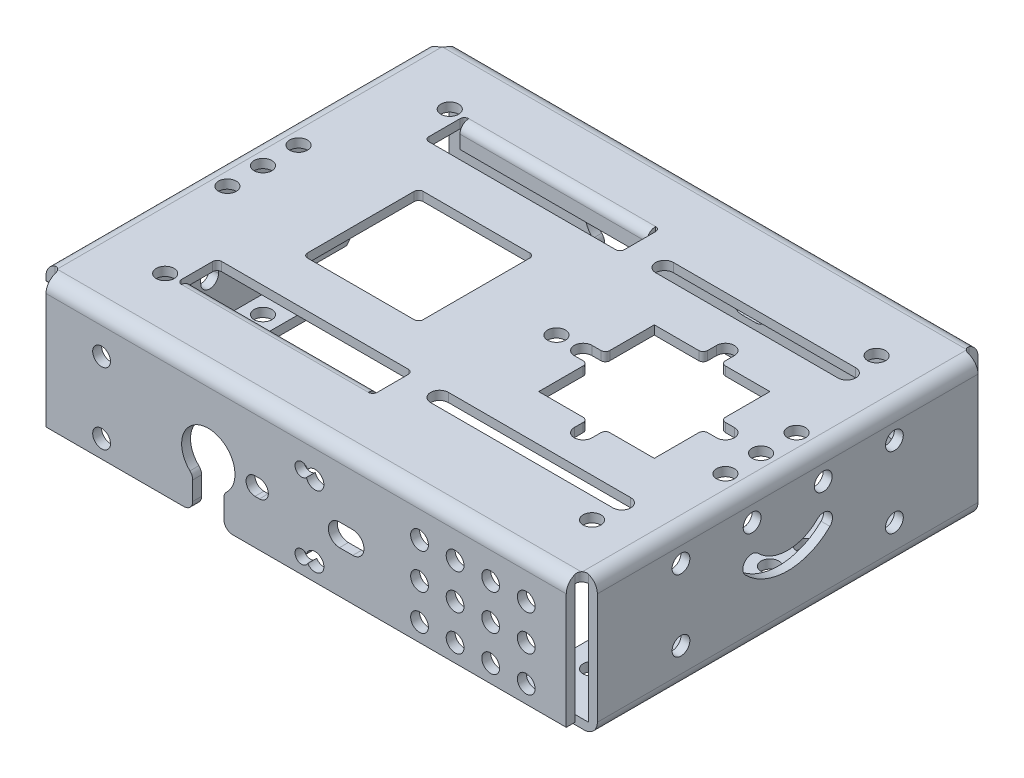
SolidWorks part; units mm, degrees
note: The reader was unsure of these and kept them because the rebuilt part matched: shared geometry of "草图3<2>".
ref_plane "前视基准面" through (0, 0, 0) normal (0, 0, 1) x (1, 0, 0)
ref_plane "上视基准面" through (0, 0, 0) normal (0, 1, 0) x (1, 0, 0)
ref_plane "右视基准面" through (0, 0, 0) normal (1, 0, 0) x (0, 0, -1)
other "Configuration Table"
sketch "草图1" plane through (0, 0, 0) normal (0, 1, 0) x (1, 0, 0)
  line L1 (-62, -46.3) -> (62, -46.3)
  line L2 (-62, -46.3) -> (-62, 46.3)
  line L3 (-62, 46.3) -> (62, 46.3)
  line L4 (62, -46.3) -> (62, 46.3)
  line L5 (-62, -46.3) -> (62, 46.3) construction
  line L6 (-62, 46.3) -> (62, -46.3) construction
  point P0 (0, 0)
  dimension "D1" = 124
  dimension "D2" = 92.6
extrude "凸台-拉伸1" add sketch "草图1" along normal blind 29
shell "抽壳1" thickness 2 removed face at (0, 0, 0)
sketch "草图2" plane through (62, 0, 0) normal (1, 0, 0) x (0, 0, -1)
  line L0 (0, 0) -> (0, 29) construction
  line L1 (-46.3, 0) -> (46.3, 0) construction
  line L2 (-46.3, 29) -> (46.3, 29) construction
  line L3 (-6.6708, 15.8292) -> (-9.4992, 13.0008) construction
  line L4 (6.6708, 15.8292) -> (9.4992, 13.0008) construction
  line L5 (8, 22.5) -> (-8, 22.5) construction
  circle A0 centre (-8, 22.5) radius 2
  circle A1 centre (-24, 22.5) radius 2
  circle A5 centre (-24, 6.5) radius 2
  circle A6 centre (24, 6.5) radius 2
  circle A7 centre (24, 22.5) radius 2
  circle A8 centre (8, 22.5) radius 2
  arc A9 (-6.6708, 15.8292) -> (-9.4992, 13.0008) centre (-8.085, 14.415) ccw
  arc A10 (9.4992, 13.0008) -> (6.6708, 15.8292) centre (8.085, 14.415) ccw
  arc A11 (-9.4992, 13.0008) -> (9.4992, 13.0008) centre (0, 22.5) ccw
  arc A12 (-6.6708, 15.8292) -> (6.6708, 15.8292) centre (0, 22.5) ccw
  point P34 (-8.085, 14.415)
  dimension "D1" = 4
  dimension "D2" = 4
  dimension "D5" = 4
  dimension "D7" = 16
  dimension "D3" = 16
  dimension "D4" = 8
  dimension "D6" = 6.5
  dimension "D8" = 4
  dimension "D9" = 8.085
  dimension "D10" = 90
extrude "切除-拉伸1" cut sketch "草图2" against normal blind 32
sketch "草图3" plane through (62, 0, 0) normal (1, 0, 0) x (0, 0, -1)
  line L0 (-46.3, 29) -> (46.3, 29) construction
  line L1 (-46.3, 29) -> (-42.8, 29)
  line L2 (-46.3, 29) -> (-46.3, 0)
  line L3 (-46.3, 0) -> (-42.8, 0)
  line L4 (-42.8, 29) -> (-42.8, 0)
  line L5 (-46.3, 0) -> (46.3, 0) construction
  line L6 (46.3, 29) -> (46.3, 0) construction
  line L7 (46.3, 29) -> (42.8, 29)
  line L8 (46.3, 29) -> (46.3, 0)
  line L9 (46.3, 0) -> (42.8, 0)
  line L10 (42.8, 29) -> (42.8, 0)
  line L11 (-46.3, 29) -> (-46.3, 0) construction
  dimension "D1" = 3.5
  dimension "D2" = 3.5
extrude "切除-拉伸2" cut sketch "草图3" against normal blind 3.5
extrude "切除-拉伸3" cut sketch "草图3<2>" along normal blind 3.5 from surface at -124 starting at face at (-62, 14.5, 0)
sketch "草图3<2>" plane through (62, 0, 0) normal (1, 0, 0) x (0, 0, -1) same geometry as "草图3"
sketch "草图4" plane through (-62, 0, 0) normal (-1, 0, 0) x (0, 0, 1)
  line L8 (0, 0) -> (0, 29) construction
  line L9 (-42.8, 29) -> (42.8, 29) construction
  line L10 (0, 9.1716) -> (-6, 15.1716)
  line L11 (-6, 15.1716) -> (-6, 9)
  line L12 (-10, 9) -> (-10, 20)
  line L13 (-6.5858, 21.4142) -> (0, 14.8284)
  line L14 (0, 14.8284) -> (6.5858, 21.4142)
  line L15 (10, 20) -> (10, 9)
  line L16 (6, 9) -> (6, 15.1716)
  line L17 (6, 15.1716) -> (0, 9.1716)
  line L18 (-42.8, 0) -> (42.8, 0) construction
  arc A4 (-6, 9) -> (-10, 9) centre (-8, 9) cw
  arc A5 (-10, 20) -> (-6.5858, 21.4142) centre (-8, 20) cw
  arc A6 (6.5858, 21.4142) -> (10, 20) centre (8, 20) cw
  arc A7 (10, 9) -> (6, 9) centre (8, 9) cw
  dimension "D1" = 2
  dimension "D2" = 2
  dimension "D3" = 4
  dimension "D4" = 4
  dimension "D5" = 4
  dimension "D6" = 4
  dimension "D7" = 12
  dimension "D8" = 9
  dimension "D9" = 9
  dimension "D10" = 45
extrude "切除-拉伸4" cut sketch "草图4" against normal blind 3.5
sketch "草图5" plane through (-62, 0, 0) normal (-1, 0, 0) x (0, 0, 1)
  line L0 (-42.8, 25) -> (-22.8, 0)
  line L1 (-42.8, 29) -> (-42.8, 0) construction
  line L2 (-42.8, 0) -> (42.8, 0) construction
  line L3 (-22.8, 0) -> (-13.5, 0)
  line L4 (22.8, 0) -> (42.8, 25)
  line L5 (42.8, 0) -> (42.8, 29) construction
  line L6 (42.8, 25) -> (42.8, -10.1592)
  line L7 (42.8, -10.1592) -> (-42.8, -10.1592)
  line L8 (-42.8, 25) -> (-42.8, -10.1592)
  line L9 (-44.3, 27) -> (-42.8, 27) construction
  line L10 (-13.5, 0) -> (-13.5, 3)
  line L11 (-11.5, 3) -> (-11.5, 0)
  line L12 (11.5, 0) -> (11.5, 3)
  line L13 (13.5, 3) -> (13.5, 0)
  line L14 (-11.5, 0) -> (11.5, 0)
  line L15 (13.5, 0) -> (22.8, 0)
  arc A0 (-13.5, 3) -> (-11.5, 3) centre (-12.5, 3) cw
  arc A1 (11.5, 3) -> (13.5, 3) centre (12.5, 3) cw
  dimension "D8" = 1
  dimension "D9" = 1
  dimension "D1" = 2
  dimension "D2" = 20
  dimension "D3" = 20
  dimension "D4" = 25
  dimension "D5" = 12.5
  dimension "D6" = 3
  dimension "D7" = 3
extrude "切除-拉伸5" cut sketch "草图5" against normal blind 3.5
sketch "草图6" plane through (-62, 0, 0) normal (-1, 0, 0) x (0, 0, 1)
  line L0 (11.5, 3) -> (11.5, 0) construction
  line L1 (-11.5, 0) -> (11.5, 0)
  line L2 (-11.5, 0) -> (-11.5, -2)
  line L3 (-11.5, -2) -> (11.5, -2)
  line L4 (11.5, 0) -> (11.5, -2)
  dimension "D1" = 2
extrude "凸台-拉伸2" add sketch "草图6" against normal blind 10
sketch "草图7" plane through (62, 0, 0) normal (1, 0, 0) x (0, 0, -1)
  line L0 (-42.8, 0) -> (42.8, 0) construction
  line L1 (-42.8, 0) -> (42.8, 0)
  line L2 (-42.8, 0) -> (-42.8, -2)
  line L3 (-42.8, -2) -> (42.8, -2)
  line L4 (42.8, 0) -> (42.8, -2)
  line L5 (42.8, 29) -> (42.8, 0) construction
  line L6 (-42.8, 0) -> (-42.8, 29) construction
  dimension "D1" = 2
extrude "凸台-拉伸3" add sketch "草图7" against normal blind 18
fillet "圆角2" radius 3 6 edges at (62, 29, 0) (0, 29, -46.3) (0, 29, 46.3) (-62, 29, 0) (62, -2, 0) (-62, -2, 0)
fillet "圆角3" radius 1.5 4 edges at (58.5, 28, -42.8) (-58.5, 28, 42.8) (-58.5, 28, -42.8) (58.5, 28, 42.8)
fillet "圆角4" radius 1 3 edges at (-61, 14.8284, 0) (-61, 15.1716, 6) (-61, 15.1716, -6)
sketch "草图8" plane through (0, 0, 0) normal (0, -1, 0) x (1, 0, 0)
  line L1 (44, 42.8) -> (44, -42.8) construction
  line L2 (-56, 0) -> (44, 0) construction
  line L3 (-52, -11.5) -> (-52, 11.5) construction
  circle A0 centre (-56, 0) radius 2
  circle A1 centre (-56, 8) radius 2
  circle A2 centre (-56, -8) radius 2
  circle A3 centre (50, 0) radius 2
  circle A4 centre (50, 8) radius 2
  circle A5 centre (50, -8) radius 2
  circle A6 centre (50, -16) radius 2
  circle A7 centre (50, 16) radius 2
  circle A8 centre (50, 32) radius 2
  circle A9 centre (50, -32) radius 2
  dimension "D1" = 4
  dimension "D2" = 4
  dimension "D5" = 4
  dimension "D8" = 4
  dimension "D3" = 4
  dimension "D4" = 4
  dimension "D6" = 4
  dimension "D7" = 4
  dimension "D9" = 4
  dimension "D10" = 4
  dimension "D11" = 8
  dimension "D12" = 8
  dimension "D13" = 8
  dimension "D14" = 8
  dimension "D15" = 16
  dimension "D16" = 16
  dimension "D17" = 6
  dimension "D18" = 8
  dimension "D19" = 8
  dimension "D20" = 4
extrude "切除-拉伸6" cut sketch "草图8" along normal blind 3
sketch "草图9" plane through (0, 0, -46.3) normal (0, 0, -1) x (-1, 0, 0)
  line L4 (0, 26) -> (0, 0) construction
  line L15 (58.5, 26) -> (-58.5, 26) construction
  line L16 (-25.5, 20) -> (-33.5, 20) construction
  line L17 (46, 12) -> (22, 12) construction
  line L18 (46, 20) -> (46, 4) construction
  line L19 (18.5, 0) -> (18.5, 7.1266)
  line L20 (25.5, 0) -> (18.5, 0)
  line L21 (25.5, 7.1266) -> (25.5, 0)
  line L22 (-7.5, 12) -> (-10.5, 12) construction
  line L23 (-7.5, 14.5) -> (-10.5, 14.5)
  line L24 (-7.5, 9.5) -> (-10.5, 9.5)
  line L25 (11.5, 12) -> (10.5, 12) construction
  line L26 (11.5, 14) -> (10.5, 14)
  line L27 (11.5, 10) -> (10.5, 10)
  circle A25 centre (-25.5, 4) radius 2
  circle A26 centre (-25.5, 12) radius 2
  circle A27 centre (-49.5, 4) radius 2
  circle A28 centre (-41.5, 4) radius 2
  circle A29 centre (-33.5, 4) radius 2
  circle A30 centre (-49.5, 12) radius 2
  circle A31 centre (-41.5, 12) radius 2
  circle A32 centre (-33.5, 12) radius 2
  circle A33 centre (-49.5, 20) radius 2
  circle A34 centre (-41.5, 20) radius 2
  circle A35 centre (-33.5, 20) radius 2
  circle A36 centre (-25.5, 20) radius 2
  arc A37 (-0.0758, 19.4547) -> (-0.3567, 21.1399) centre (1, 20.5) ccw
  arc A38 (-0.3567, 21.1399) -> (-0.0758, 19.4547) centre (-2, 20) ccw
  arc A39 (-0.3567, 2.8601) -> (-0.0758, 4.5453) centre (-2, 4) cw
  arc A40 (-0.0758, 4.5453) -> (-0.3567, 2.8601) centre (1, 3.5) cw
  arc A41 (18.5, 7.1266) -> (25.5, 7.1266) centre (22, 12) cw
  circle A42 centre (46, 20) radius 2
  circle A43 centre (46, 4) radius 2
  arc A44 (-7.5, 14.5) -> (-7.5, 9.5) centre (-7.5, 12) cw
  arc A45 (-10.5, 9.5) -> (-10.5, 14.5) centre (-10.5, 12) cw
  arc A46 (11.5, 14) -> (11.5, 10) centre (11.5, 12) cw
  arc A47 (10.5, 10) -> (10.5, 14) centre (10.5, 12) cw
  point P127 (-9, 12)
  point P134 (11, 12)
extrude "切除-拉伸7" cut sketch "草图9" against normal through all
fillet "圆角5" radius 2 8 edges at (-18.5, 0, -45.3) (-25.5, 0, -45.3) (-18.5, 0, 45.3) (-25.5, 0, 45.3) (-25.5, 7.1266, 45.3) (-18.5, 7.1266, 45.3) (-18.5, 7.1266, -45.3) (-25.5, 7.1266, -45.3)
sketch "草图26" plane through (0, 29, 0) normal (0, 1, 0) x (1, 0, 0)
  line L0 (0, -43.3) -> (0, 43.3) construction
  line L1 (62, 42.8) -> (62, -42.8) construction
  line L2 (9, 25.3) -> (50, 25.3) construction
  line L3 (-42, 32.3) -> (0, 32.3)
  line L4 (-43, 31.3) -> (-43, 24.3)
  line L5 (-42, 23.3) -> (0, 23.3)
  line L6 (1, 31.3) -> (1, 24.3)
  line L7 (9, 27.3) -> (50, 27.3)
  line L8 (9, 23.3) -> (50, 23.3)
  line L9 (-58.882, -43.3) -> (58.882, -43.3) construction
  line L10 (-33, 13) -> (-9, 13)
  line L11 (-34, 12) -> (-34, -12)
  line L12 (-33, -13) -> (-9, -13)
  line L13 (-8, 12) -> (-8, -12)
  line L14 (19, 13) -> (29, 13)
  line L15 (19, 13) -> (19, 3)
  line L16 (19, -13) -> (29, -13)
  line L17 (45, 13) -> (45, 3)
  line L18 (58.882, 43.3) -> (-58.882, 43.3) construction
  line L19 (0.627, 0) -> (59, 0) construction
  line L20 (59, -43.182) -> (59, 43.182) construction
  line L21 (-62, -42.8) -> (-62, 42.8) construction
  line L22 (16, 0) -> (19, 0) construction
  line L23 (16, 2) -> (18, 2)
  line L24 (16, -2) -> (18, -2)
  line L25 (19, -3) -> (19, -13)
  line L26 (19, 13) -> (45, -13) construction
  line L27 (30, 16) -> (30, 14)
  line L28 (34, 16) -> (34, 14)
  line L29 (48, 2) -> (46, 2)
  line L30 (48, -2) -> (46, -2)
  line L31 (34, -16) -> (34, -14)
  line L32 (30, -16) -> (30, -14)
  line L33 (35, 13) -> (45, 13)
  line L34 (45, -3) -> (45, -13)
  line L35 (35, -13) -> (45, -13)
  line L36 (-58.5, 46.3) -> (58.5, 46.3) construction
  line L37 (1, -31.3) -> (1, -24.3)
  line L38 (-42, -23.3) -> (0, -23.3)
  line L39 (-43, -31.3) -> (-43, -24.3)
  line L40 (-42, -32.3) -> (0, -32.3)
  line L41 (9, -25.3) -> (50, -25.3) construction
  line L42 (9, -27.3) -> (50, -27.3)
  line L43 (9, -23.3) -> (50, -23.3)
  line L44 (-46, -32) -> (-46, 32) construction
  circle A0 centre (56, 0) radius 2
  circle A1 centre (56, 8) radius 2
  circle A2 centre (56, -8) radius 2
  circle A3 centre (-56, -8) radius 2
  circle A4 centre (-56, 8) radius 2
  circle A5 centre (-56, 0) radius 2
  arc A6 (9, 27.3) -> (9, 23.3) centre (9, 25.3) ccw
  arc A7 (50, 23.3) -> (50, 27.3) centre (50, 25.3) ccw
  circle A8 centre (10, 0) radius 2
  arc A9 (16, 2) -> (16, -2) centre (16, 0) ccw
  arc A10 (34, 16) -> (30, 16) centre (32, 16) ccw
  arc A11 (48, -2) -> (48, 2) centre (48, 0) ccw
  arc A12 (30, -16) -> (34, -16) centre (32, -16) ccw
  arc A13 (29, 13) -> (30, 14) centre (29, 14) ccw
  arc A14 (35, 13) -> (34, 14) centre (35, 14) cw
  arc A15 (45, 3) -> (46, 2) centre (46, 3) ccw
  arc A16 (46, -2) -> (45, -3) centre (46, -3) ccw
  arc A17 (35, -13) -> (34, -14) centre (35, -14) ccw
  arc A18 (30, -14) -> (29, -13) centre (29, -14) ccw
  arc A19 (19, -3) -> (18, -2) centre (18, -3) ccw
  arc A20 (18, 2) -> (19, 3) centre (18, 3) ccw
  arc A21 (9, -27.3) -> (9, -23.3) centre (9, -25.3) cw
  arc A22 (50, -23.3) -> (50, -27.3) centre (50, -25.3) cw
  circle A23 centre (-46, 32) radius 2
  circle A24 centre (50, 32) radius 2
  circle A25 centre (50, -32) radius 2
  circle A26 centre (-46, -32) radius 2
  arc A27 (-33, -13) -> (-34, -12) centre (-33, -12) cw
  arc A28 (-33, 13) -> (-34, 12) centre (-33, 12) ccw
  arc A29 (-8, 12) -> (-9, 13) centre (-9, 12) ccw
  arc A30 (-8, -12) -> (-9, -13) centre (-9, -12) cw
  arc A31 (1, -24.3) -> (0, -23.3) centre (0, -24.3) ccw
  arc A32 (0, -32.3) -> (1, -31.3) centre (0, -31.3) ccw
  arc A33 (-43, -31.3) -> (-42, -32.3) centre (-42, -31.3) ccw
  arc A34 (-42, -23.3) -> (-43, -24.3) centre (-42, -24.3) ccw
  arc A35 (1, 31.3) -> (0, 32.3) centre (0, 31.3) ccw
  arc A36 (1, 24.3) -> (0, 23.3) centre (0, 24.3) cw
  arc A37 (-43, 24.3) -> (-42, 23.3) centre (-42, 24.3) ccw
  arc A38 (-42, 32.3) -> (-43, 31.3) centre (-42, 31.3) ccw
  point P23 (29.5, 25.3)
  point P38 (17.5, 0)
  point P39 (-8, 0)
  point P42 (32, 0)
  point P75 (32, 0)
  point P98 (29.5, -25.3)
  point P111 (-46, 0)
  point P118 (-34, -13)
  point P121 (-34, 13)
  point P124 (-8, 13)
  point P129 (1, -23.3)
  point P132 (1, -32.3)
  point P135 (-43, -32.3)
  point P138 (-43, -23.3)
  point P141 (1, 32.3)
  point P144 (1, 23.3)
  point P147 (-43, 23.3)
  point P150 (-43, 32.3)
  dimension "D1" = 4
  dimension "D2" = 4
  dimension "D3" = 4
  dimension "D13" = 4
  dimension "D15" = 2
  dimension "D19" = 1
  dimension "D20" = 2
  dimension "D26" = 4
  dimension "D27" = 4
  dimension "D28" = 4
  dimension "D29" = 4
  dimension "D33" = 1
  dimension "D4" = 16
  dimension "D5" = 8
  dimension "D6" = 6
  dimension "D7" = 26
  dimension "D8" = 26
  dimension "D9" = 17
  dimension "D10" = 26
  dimension "D11" = 26
  dimension "D12" = 28
  dimension "D16" = 3
  dimension "D17" = 13
  dimension "D21" = 9
  dimension "D22" = 21
  dimension "D23" = 44
  dimension "D24" = 41
  dimension "D25" = 8
  dimension "D30" = 96
  dimension "D31" = 64
  dimension "D14" = 56
  dimension "D32" = 6
  dimension "D18" = 4
extrude "切除-拉伸8" cut sketch "草图26" against normal blind 3
sketch "草图27" plane through (0, 29, 0) normal (0, 1, 0) x (1, 0, 0)
  line L0 (0, 0) -> (-56, 0) construction
  line L1 (-42, 32.3) -> (0, 32.3)
  line L2 (-42, 32.3) -> (-42, 30.3)
  line L3 (-42, 30.3) -> (0, 30.3)
  line L4 (0, 32.3) -> (0, 30.3)
  line L5 (0, -32.3) -> (0, -30.3)
  line L6 (-42, -30.3) -> (0, -30.3)
  line L7 (-42, -32.3) -> (-42, -30.3)
  line L8 (-42, -32.3) -> (0, -32.3)
  dimension "D1" = 2
extrude "凸台-拉伸4" add sketch "草图27" against normal blind 5
fillet "圆角6" radius 2 2 edges at (-21, 29, 30.3) (-21, 29, -30.3)
thread "螺纹线7" [suppressed] pitch 0.25 start angle 0, offset 0, length 2, pitch 0.25, diameter 4
ref_plane "基准面7" [suppressed] through (-50.5, 32, -32) normal (0, 0, 1) x (-1, 0, 0)
sketch "螺纹线轮廓7" [suppressed] plane through (-50.5, 32, -32) normal (0, 0, 1) x (-1, 0, 0)
  line L0 (0, 0) -> (0, 0.25) construction
  line L1 (0, 0) -> (0.1353, 0.0781)
  line L2 (0.1353, 0.0781) -> (0.1353, 0.1094)
  line L3 (0.1353, 0.1094) -> (0, 0.1875)
  line L4 (0.1353, 0.0937) -> (0, 0.0937) construction
  line L11 (0, 0) -> (0, 0.1875)
  point P2 (0, 0)
  dimension "Pitch" = 0.25
  dimension "Profile_Angle" = 60
  dimension "Profile_Land" = 0.0312
  dimension "Profile_Height" = 0.1353
thread "螺纹线20" [suppressed] pitch 0.25 start angle 0, offset 0, length 2, pitch 0.25, diameter 4
ref_plane "基准面20" [suppressed] through (52, 0, 16) normal (0, 0, 1) x (1, 0, 0)
sketch "螺纹线轮廓20" [suppressed] plane through (52, 0, 16) normal (0, 0, 1) x (1, 0, 0)
  line L0 (0, 0) -> (0, 0.25) construction
  line L1 (0, 0) -> (0.1353, 0.0781)
  line L2 (0.1353, 0.0781) -> (0.1353, 0.1094)
  line L3 (0.1353, 0.1094) -> (0, 0.1875)
  line L4 (0.1353, 0.0937) -> (0, 0.0937) construction
  line L11 (0, 0) -> (0, 0.1875)
  point P2 (0, 0)
  dimension "Pitch" = 0.25
  dimension "Profile_Angle" = 60
  dimension "Profile_Land" = 0.0312
  dimension "Profile_Height" = 0.1353
thread "螺纹线19" [suppressed] pitch 0.25 start angle 0, offset 0, length 2, pitch 0.25, diameter 4
ref_plane "基准面19" [suppressed] through (52, 0, 8) normal (0, 0, 1) x (1, 0, 0)
sketch "螺纹线轮廓19" [suppressed] plane through (52, 0, 8) normal (0, 0, 1) x (1, 0, 0)
  line L0 (0, 0) -> (0, 0.25) construction
  line L1 (0, 0) -> (0.1353, 0.0781)
  line L2 (0.1353, 0.0781) -> (0.1353, 0.1094)
  line L3 (0.1353, 0.1094) -> (0, 0.1875)
  line L4 (0.1353, 0.0937) -> (0, 0.0937) construction
  line L11 (0, 0) -> (0, 0.1875)
  point P2 (0, 0)
  dimension "Pitch" = 0.25
  dimension "Profile_Angle" = 60
  dimension "Profile_Land" = 0.0312
  dimension "Profile_Height" = 0.1353
thread "螺纹线18" [suppressed] pitch 0.25 start angle 0, offset 0, length 2, pitch 0.25, diameter 4
ref_plane "基准面18" [suppressed] through (52, 0, -8) normal (0, 0, 1) x (1, 0, 0)
sketch "螺纹线轮廓18" [suppressed] plane through (52, 0, -8) normal (0, 0, 1) x (1, 0, 0)
  line L0 (0, 0) -> (0, 0.25) construction
  line L1 (0, 0) -> (0.1353, 0.0781)
  line L2 (0.1353, 0.0781) -> (0.1353, 0.1094)
  line L3 (0.1353, 0.1094) -> (0, 0.1875)
  line L4 (0.1353, 0.0937) -> (0, 0.0937) construction
  line L11 (0, 0) -> (0, 0.1875)
  point P2 (0, 0)
  dimension "Pitch" = 0.25
  dimension "Profile_Angle" = 60
  dimension "Profile_Land" = 0.0312
  dimension "Profile_Height" = 0.1353
thread "螺纹线17" [suppressed] pitch 0.25 start angle 0, offset 0, length 2, pitch 0.25, diameter 4
ref_plane "基准面17" [suppressed] through (52, 0, -16) normal (0, 0, 1) x (1, 0, 0)
sketch "螺纹线轮廓17" [suppressed] plane through (52, 0, -16) normal (0, 0, 1) x (1, 0, 0)
  line L0 (0, 0) -> (0, 0.25) construction
  line L1 (0, 0) -> (0.1353, 0.0781)
  line L2 (0.1353, 0.0781) -> (0.1353, 0.1094)
  line L3 (0.1353, 0.1094) -> (0, 0.1875)
  line L4 (0.1353, 0.0937) -> (0, 0.0937) construction
  line L11 (0, 0) -> (0, 0.1875)
  point P2 (0, 0)
  dimension "Pitch" = 0.25
  dimension "Profile_Angle" = 60
  dimension "Profile_Land" = 0.0312
  dimension "Profile_Height" = 0.1353
thread "螺纹线16" [suppressed] pitch 0.25 start angle 0, offset 0, length 2, pitch 0.25, diameter 4
ref_plane "基准面16" [suppressed] through (-54, 0, 8) normal (0, 0, 1) x (1, 0, 0)
sketch "螺纹线轮廓16" [suppressed] plane through (-54, 0, 8) normal (0, 0, 1) x (1, 0, 0)
  line L0 (0, 0) -> (0, 0.25) construction
  line L1 (0, 0) -> (0.1353, 0.0781)
  line L2 (0.1353, 0.0781) -> (0.1353, 0.1094)
  line L3 (0.1353, 0.1094) -> (0, 0.1875)
  line L4 (0.1353, 0.0937) -> (0, 0.0937) construction
  line L11 (0, 0) -> (0, 0.1875)
  point P2 (0, 0)
  dimension "Pitch" = 0.25
  dimension "Profile_Angle" = 60
  dimension "Profile_Land" = 0.0312
  dimension "Profile_Height" = 0.1353
thread "螺纹线15" [suppressed] pitch 0.25 start angle 0, offset 0, length 2, pitch 0.25, diameter 4
ref_plane "基准面15" [suppressed] through (-54, 0, -8) normal (0, 0, 1) x (1, 0, 0)
sketch "螺纹线轮廓15" [suppressed] plane through (-54, 0, -8) normal (0, 0, 1) x (1, 0, 0)
  line L0 (0, 0) -> (0, 0.25) construction
  line L1 (0, 0) -> (0.1353, 0.0781)
  line L2 (0.1353, 0.0781) -> (0.1353, 0.1094)
  line L3 (0.1353, 0.1094) -> (0, 0.1875)
  line L4 (0.1353, 0.0937) -> (0, 0.0937) construction
  line L11 (0, 0) -> (0, 0.1875)
  point P2 (0, 0)
  dimension "Pitch" = 0.25
  dimension "Profile_Angle" = 60
  dimension "Profile_Land" = 0.0312
  dimension "Profile_Height" = 0.1353
thread "螺纹线13" [suppressed] pitch 0.25 start angle 0, offset 0, length 2, pitch 0.25, diameter 4
ref_plane "基准面13" [suppressed] through (54, 32, -8) normal (0, 0, 1) x (-1, 0, 0)
sketch "螺纹线轮廓13" [suppressed] plane through (54, 32, -8) normal (0, 0, 1) x (-1, 0, 0)
  line L0 (0, 0) -> (0, 0.25) construction
  line L1 (0, 0) -> (0.1353, 0.0781)
  line L2 (0.1353, 0.0781) -> (0.1353, 0.1094)
  line L3 (0.1353, 0.1094) -> (0, 0.1875)
  line L4 (0.1353, 0.0937) -> (0, 0.0937) construction
  line L11 (0, 0) -> (0, 0.1875)
  point P2 (0, 0)
  dimension "Pitch" = 0.25
  dimension "Profile_Angle" = 60
  dimension "Profile_Land" = 0.0312
  dimension "Profile_Height" = 0.1353
thread "螺纹线12" [suppressed] pitch 0.25 start angle 0, offset 0, length 2, pitch 0.25, diameter 4
ref_plane "基准面12" [suppressed] through (-58, 32, 8) normal (0, 0, 1) x (-1, 0, 0)
sketch "螺纹线轮廓12" [suppressed] plane through (-58, 32, 8) normal (0, 0, 1) x (-1, 0, 0)
  line L0 (0, 0) -> (0, 0.25) construction
  line L1 (0, 0) -> (0.1353, 0.0781)
  line L2 (0.1353, 0.0781) -> (0.1353, 0.1094)
  line L3 (0.1353, 0.1094) -> (0, 0.1875)
  line L4 (0.1353, 0.0937) -> (0, 0.0937) construction
  line L11 (0, 0) -> (0, 0.1875)
  point P2 (0, 0)
  dimension "Pitch" = 0.25
  dimension "Profile_Angle" = 60
  dimension "Profile_Land" = 0.0312
  dimension "Profile_Height" = 0.1353
thread "螺纹线11" [suppressed] pitch 0.25 start angle 0, offset 0, length 2, pitch 0.25, diameter 4
ref_plane "基准面11" [suppressed] through (-58, 32, -8) normal (0, 0, 1) x (-1, 0, 0)
sketch "螺纹线轮廓11" [suppressed] plane through (-58, 32, -8) normal (0, 0, 1) x (-1, 0, 0)
  line L0 (0, 0) -> (0, 0.25) construction
  line L1 (0, 0) -> (0.1353, 0.0781)
  line L2 (0.1353, 0.0781) -> (0.1353, 0.1094)
  line L3 (0.1353, 0.1094) -> (0, 0.1875)
  line L4 (0.1353, 0.0937) -> (0, 0.0937) construction
  line L11 (0, 0) -> (0, 0.1875)
  point P2 (0, 0)
  dimension "Pitch" = 0.25
  dimension "Profile_Angle" = 60
  dimension "Profile_Land" = 0.0312
  dimension "Profile_Height" = 0.1353
thread "螺纹线10" [suppressed] pitch 0.25 start angle 0, offset 0, length 2, pitch 0.25, diameter 4
ref_plane "基准面10" [suppressed] through (45.5, 32, 32) normal (0, 0, 1) x (-1, 0, 0)
sketch "螺纹线轮廓10" [suppressed] plane through (45.5, 32, 32) normal (0, 0, 1) x (-1, 0, 0)
  line L0 (0, 0) -> (0, 0.25) construction
  line L1 (0, 0) -> (0.1353, 0.0781)
  line L2 (0.1353, 0.0781) -> (0.1353, 0.1094)
  line L3 (0.1353, 0.1094) -> (0, 0.1875)
  line L4 (0.1353, 0.0937) -> (0, 0.0937) construction
  line L11 (0, 0) -> (0, 0.1875)
  point P2 (0, 0)
  dimension "Pitch" = 0.25
  dimension "Profile_Angle" = 60
  dimension "Profile_Land" = 0.0312
  dimension "Profile_Height" = 0.1353
thread "螺纹线9" [suppressed] pitch 0.25 start angle 0, offset 0, length 2, pitch 0.25, diameter 4
ref_plane "基准面9" [suppressed] through (-50.5, 32, 32) normal (0, 0, 1) x (-1, 0, 0)
sketch "螺纹线轮廓9" [suppressed] plane through (-50.5, 32, 32) normal (0, 0, 1) x (-1, 0, 0)
  line L0 (0, 0) -> (0, 0.25) construction
  line L1 (0, 0) -> (0.1353, 0.0781)
  line L2 (0.1353, 0.0781) -> (0.1353, 0.1094)
  line L3 (0.1353, 0.1094) -> (0, 0.1875)
  line L4 (0.1353, 0.0937) -> (0, 0.0937) construction
  line L11 (0, 0) -> (0, 0.1875)
  point P2 (0, 0)
  dimension "Pitch" = 0.25
  dimension "Profile_Angle" = 60
  dimension "Profile_Land" = 0.0312
  dimension "Profile_Height" = 0.1353
thread "螺纹线8" [suppressed] pitch 0.25 start angle 0, offset 0, length 2, pitch 0.25, diameter 4
ref_plane "基准面8" [suppressed] through (45.5, 32, -32) normal (0, 0, 1) x (-1, 0, 0)
sketch "螺纹线轮廓8" [suppressed] plane through (45.5, 32, -32) normal (0, 0, 1) x (-1, 0, 0)
  line L0 (0, 0) -> (0, 0.25) construction
  line L1 (0, 0) -> (0.1353, 0.0781)
  line L2 (0.1353, 0.0781) -> (0.1353, 0.1094)
  line L3 (0.1353, 0.1094) -> (0, 0.1875)
  line L4 (0.1353, 0.0937) -> (0, 0.0937) construction
  line L11 (0, 0) -> (0, 0.1875)
  point P2 (0, 0)
  dimension "Pitch" = 0.25
  dimension "Profile_Angle" = 60
  dimension "Profile_Land" = 0.0312
  dimension "Profile_Height" = 0.1353
thread "螺纹线14" [suppressed] pitch 0.25 start angle 0, offset 0, length 2, pitch 0.25, diameter 4
ref_plane "基准面14" [suppressed] through (54, 32, 8) normal (0, 0, 1) x (-1, 0, 0)
sketch "螺纹线轮廓14" [suppressed] plane through (54, 32, 8) normal (0, 0, 1) x (-1, 0, 0)
  line L0 (0, 0) -> (0, 0.25) construction
  line L1 (0, 0) -> (0.1353, 0.0781)
  line L2 (0.1353, 0.0781) -> (0.1353, 0.1094)
  line L3 (0.1353, 0.1094) -> (0, 0.1875)
  line L4 (0.1353, 0.0937) -> (0, 0.0937) construction
  line L11 (0, 0) -> (0, 0.1875)
  point P2 (0, 0)
  dimension "Pitch" = 0.25
  dimension "Profile_Angle" = 60
  dimension "Profile_Land" = 0.0312
  dimension "Profile_Height" = 0.1353
thread "螺纹线1" [suppressed] pitch 0.25 start angle 0, offset 0, length 2, pitch 0.25, diameter 4
ref_plane "基准面1" [suppressed] through (62, 25.5, 26) normal (0, -1, 0) x (0, 0, 1)
sketch "螺纹线轮廓1" [suppressed] plane through (62, 25.5, 26) normal (0, -1, 0) x (0, 0, 1)
  line L0 (0, 0) -> (0, 0.25) construction
  line L1 (0, 0) -> (0.1353, 0.0781)
  line L2 (0.1353, 0.0781) -> (0.1353, 0.1094)
  line L3 (0.1353, 0.1094) -> (0, 0.1875)
  line L4 (0.1353, 0.0937) -> (0, 0.0937) construction
  line L11 (0, 0) -> (0, 0.1875)
  point P2 (0, 0)
  dimension "Pitch" = 0.25
  dimension "Profile_Angle" = 60
  dimension "Profile_Land" = 0.0312
  dimension "Profile_Height" = 0.1353
thread "螺纹线3" [suppressed] pitch 0.25 start angle 0, offset 0, length 2, pitch 0.25, diameter 4
ref_plane "基准面3" [suppressed] through (62, 25.5, -6) normal (0, -1, 0) x (0, 0, 1)
sketch "螺纹线轮廓3" [suppressed] plane through (62, 25.5, -6) normal (0, -1, 0) x (0, 0, 1)
  line L0 (0, 0) -> (0, 0.25) construction
  line L1 (0, 0) -> (0.1353, 0.0781)
  line L2 (0.1353, 0.0781) -> (0.1353, 0.1094)
  line L3 (0.1353, 0.1094) -> (0, 0.1875)
  line L4 (0.1353, 0.0937) -> (0, 0.0937) construction
  line L11 (0, 0) -> (0, 0.1875)
  point P2 (0, 0)
  dimension "Pitch" = 0.25
  dimension "Profile_Angle" = 60
  dimension "Profile_Land" = 0.0312
  dimension "Profile_Height" = 0.1353
thread "螺纹线4" [suppressed] pitch 0.25 start angle 0, offset 0, length 2, pitch 0.25, diameter 4
ref_plane "基准面4" [suppressed] through (62, 25.5, -22) normal (0, -1, 0) x (0, 0, 1)
sketch "螺纹线轮廓4" [suppressed] plane through (62, 25.5, -22) normal (0, -1, 0) x (0, 0, 1)
  line L0 (0, 0) -> (0, 0.25) construction
  line L1 (0, 0) -> (0.1353, 0.0781)
  line L2 (0.1353, 0.0781) -> (0.1353, 0.1094)
  line L3 (0.1353, 0.1094) -> (0, 0.1875)
  line L4 (0.1353, 0.0937) -> (0, 0.0937) construction
  line L11 (0, 0) -> (0, 0.1875)
  point P2 (0, 0)
  dimension "Pitch" = 0.25
  dimension "Profile_Angle" = 60
  dimension "Profile_Land" = 0.0312
  dimension "Profile_Height" = 0.1353
thread "螺纹线5" [suppressed] pitch 0.25 start angle 0, offset 0, length 2, pitch 0.25, diameter 4
ref_plane "基准面5" [suppressed] through (62, 9.5, 26) normal (0, -1, 0) x (0, 0, 1)
sketch "螺纹线轮廓5" [suppressed] plane through (62, 9.5, 26) normal (0, -1, 0) x (0, 0, 1)
  line L0 (0, 0) -> (0, 0.25) construction
  line L1 (0, 0) -> (0.1353, 0.0781)
  line L2 (0.1353, 0.0781) -> (0.1353, 0.1094)
  line L3 (0.1353, 0.1094) -> (0, 0.1875)
  line L4 (0.1353, 0.0937) -> (0, 0.0937) construction
  line L11 (0, 0) -> (0, 0.1875)
  point P2 (0, 0)
  dimension "Pitch" = 0.25
  dimension "Profile_Angle" = 60
  dimension "Profile_Land" = 0.0312
  dimension "Profile_Height" = 0.1353
thread "螺纹线6" [suppressed] pitch 0.25 start angle 0, offset 0, length 2, pitch 0.25, diameter 4
ref_plane "基准面6" [suppressed] through (62, 9.5, -22) normal (0, -1, 0) x (0, 0, 1)
sketch "螺纹线轮廓6" [suppressed] plane through (62, 9.5, -22) normal (0, -1, 0) x (0, 0, 1)
  line L0 (0, 0) -> (0, 0.25) construction
  line L1 (0, 0) -> (0.1353, 0.0781)
  line L2 (0.1353, 0.0781) -> (0.1353, 0.1094)
  line L3 (0.1353, 0.1094) -> (0, 0.1875)
  line L4 (0.1353, 0.0937) -> (0, 0.0937) construction
  line L11 (0, 0) -> (0, 0.1875)
  point P2 (0, 0)
  dimension "Pitch" = 0.25
  dimension "Profile_Angle" = 60
  dimension "Profile_Land" = 0.0312
  dimension "Profile_Height" = 0.1353
thread "螺纹线2" [suppressed] pitch 0.25 start angle 0, offset 0, length 2, pitch 0.25, diameter 4
ref_plane "基准面2" [suppressed] through (62, 25.5, 10) normal (0, -1, 0) x (0, 0, 1)
sketch "螺纹线轮廓2" [suppressed] plane through (62, 25.5, 10) normal (0, -1, 0) x (0, 0, 1)
  line L0 (0, 0) -> (0, 0.25) construction
  line L1 (0, 0) -> (0.1353, 0.0781)
  line L2 (0.1353, 0.0781) -> (0.1353, 0.1094)
  line L3 (0.1353, 0.1094) -> (0, 0.1875)
  line L4 (0.1353, 0.0937) -> (0, 0.0937) construction
  line L11 (0, 0) -> (0, 0.1875)
  point P2 (0, 0)
  dimension "Pitch" = 0.25
  dimension "Profile_Angle" = 60
  dimension "Profile_Land" = 0.0312
  dimension "Profile_Height" = 0.1353
equation "\"D2@草图2\"=\"D1@草图2\""
equation "\"D5@草图2\"=\"D1@草图2\""
equation "\"D3@草图2\"=\"D7@草图2\""
equation "\"D4@草图2\"=\"D7@草图2\"/2"
equation "\"D8@草图2\"=\"D1@草图2\""
equation "\"D4@草图4\"=\"D3@草图4\""
equation "\"D5@草图4\"=\"D3@草图4\""
equation "\"D6@草图4\"=\"D3@草图4\""
equation "\"D5@草图5\"=\"D4@草图5\"/2"
equation "\"D7@草图5\"=\"D6@草图5\""
equation "\"D2@草图8\"=\"D1@草图8\""
equation "\"D3@草图8\"=\"D1@草图8\""
equation "\"D4@草图8\"=\"D1@草图8\""
equation "\"D5@草图8\"=\"D1@草图8\""
equation "\"D6@草图8\"=\"D1@草图8\""
equation "\"D7@草图8\"=\"D1@草图8\""
equation "\"D8@草图8\"=\"D1@草图8\""
equation "\"D9@草图8\"=\"D1@草图8\""
equation "\"D10@草图8\"=\"D1@草图8\""
equation "\"D12@草图8\"=\"D11@草图8\""
equation "\"D13@草图8\"=\"D11@草图8\""
equation "\"D14@草图8\"=\"D11@草图8\""
equation "\"D15@草图8\"=\"D11@草图8\"*2"
equation "\"D16@草图8\"=\"D15@草图8\""
equation "\"D18@草图8\"=\"D11@草图8\""
equation "\"D17@草图26\"=\"D8@草图26\"/2"
